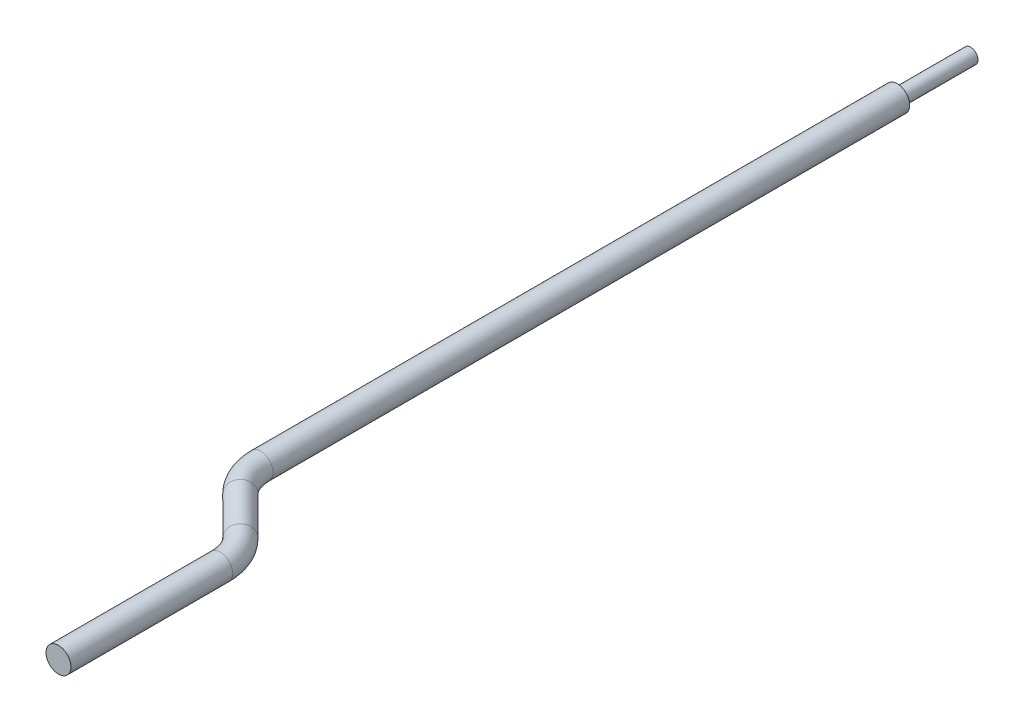
SolidWorks part; units mm, degrees
ref_plane "Front" through (0, 0, 0) normal (0, 0, 1) x (1, 0, 0)
ref_plane "Top" through (0, 0, 0) normal (0, 1, 0) x (1, 0, 0)
ref_plane "Right" through (0, 0, 0) normal (1, 0, 0) x (0, 0, -1)
sketch "Sketch1" plane through (0, 0, 0) normal (0, 0, 1) x (1, 0, 0)
  circle A0 centre (0, 0) radius 0.6477
  dimension "D1" = 1.2954
extrude "Boss-Extrude1" add sketch "Sketch1" along normal blind 35.56
ref_axis "Axis1" through (0, 0, 50) along (0, 0, -1)
sketch "Sketch2" plane through (0, 0, 0) normal (0, 1, 0) x (1, 0, 0)
  line L0 (3.4798, -50.8) -> (3.4798, -42.414)
  line L1 (0, -35.56) -> (0, -36.83)
  line L3 (-0.6477, -35.56) -> (0.6477, -35.56) construction
  line L4 (0.7439, -38.6261) -> (2.7359, -40.618)
  arc A0 (2.7359, -40.618) -> (3.4798, -42.414) centre (0.9398, -42.414) cw
  arc A1 (0, -36.83) -> (0.7439, -38.6261) centre (2.54, -36.83) ccw
  dimension "D4" = 2.54
  dimension "D1" = 15.24
  dimension "D2" = 3.4798
  dimension "D3" = 45
  dimension "D5" = 1.27
sketch "Sketch3" plane through (0, 0, 35.56) normal (0, 0, 1) x (1, 0, 0)
  circle A0 centre (0, 0) radius 0.6477
  circle A1 centre (0, 0) radius 0.6477 construction
sweep "Sweep1" add profiles "Sketch3" path "Sketch2"
sketch "Sketch4" plane through (0, 0, 0) normal (0, 0, -1) x (-1, 0, 0)
  circle A0 centre (0, 0) radius 0.381
  circle A1 centre (0, 0) radius 0.6477
  circle A2 centre (0, 0) radius 0.6477 construction
  dimension "D1" = 0.762
extrude "Cut-Extrude1" cut sketch "Sketch4" against normal blind 3.81
ref_point "Point1"
ref_point "Point2"
